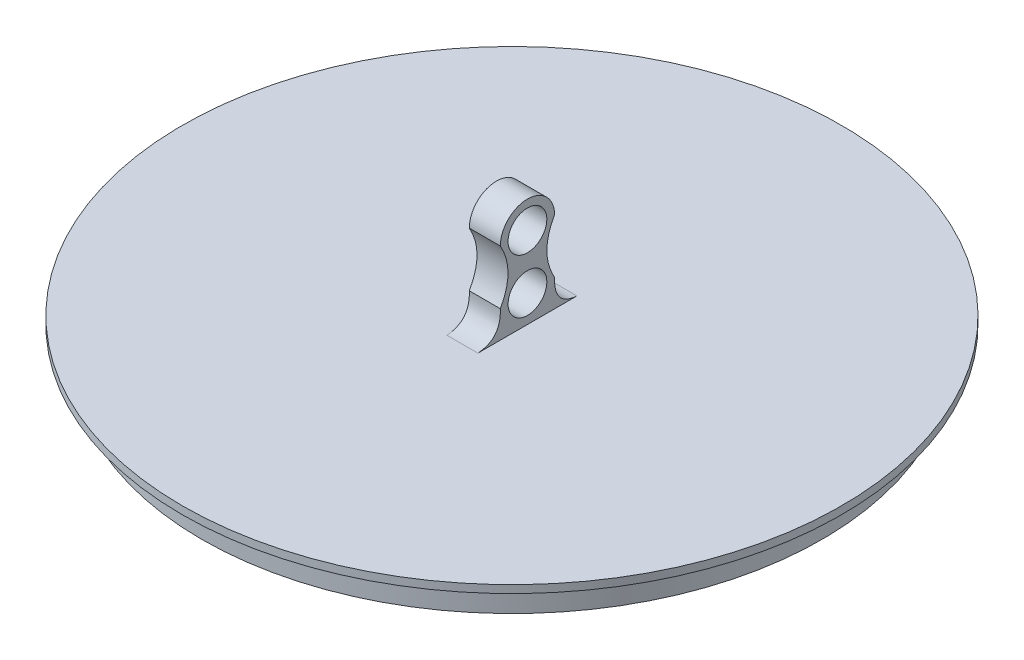
SolidWorks part; units mm, degrees
ref_plane "Спереди" through (0, 0, 0) normal (0, 0, 1) x (1, 0, 0)
ref_plane "Сверху" through (0, 0, 0) normal (0, 1, 0) x (1, 0, 0)
ref_plane "Справа" through (0, 0, 0) normal (1, 0, 0) x (0, 0, -1)
sketch "Эскиз3" plane through (0, 0, 0) normal (0, 1, 0) x (1, 0, 0)
  circle A0 centre (0, 0) radius 40
  dimension "D1" = 80
extrude "Бобышка-Вытянуть1" add sketch "Эскиз3" along normal blind 4
ref_plane "Плоскость4" through (0, 4, 0) normal (0, 1, 0) x (1, 0, 0)
sketch "Эскиз4" plane through (0, 4, 0) normal (0, 1, 0) x (1, 0, 0)
  circle A0 centre (0, 0) radius 42.5
  dimension "D1" = 85
extrude "Бобышка-Вытянуть2" add sketch "Эскиз4" along normal blind 1
sketch "Эскиз5" plane through (0, 0, 0) normal (1, 0, 0) x (0, 0, -1)
  line L4 (42.5, 5) -> (-42.5, 5) construction
  line L5 (-7.3816, 5) -> (7.3816, 5)
  circle A0 centre (0, 15.5178) radius 2.5
  circle A1 centre (0, 8.5178) radius 2.5
  arc A2 (3.5, 15.5178) -> (-3.5, 15.5178) centre (0, 15.5178) ccw
  spline S0 degree 2 poles (-3.5, 8.5178) (-3.3277, 4.7342) (-7.3816, 5) knots 0 0 0 1 1 1
  spline S1 degree 2 poles (3.5, 8.5178) (3.3277, 4.7342) (7.3816, 5) knots 0 0 0 1 1 1
  spline S2 degree 2 poles (-3.5, 15.5178) (-1.5107, 12.0178) (-3.5, 8.5178) knots 0 0 0 1 1 1
  spline S4 degree 2 poles (3.5, 15.5178) (1.5107, 12.0178) (3.5, 8.5178) knots 0 0 0 1 1 1
  dimension "D1" = 5
extrude "Бобышка-Вытянуть3" add sketch "Эскиз5" along normal blind 2 and the other way blind 2 contours S4 A2 S2 S0 L5 S1 A1 A0 region at (0, 5.934, 3.9537)
